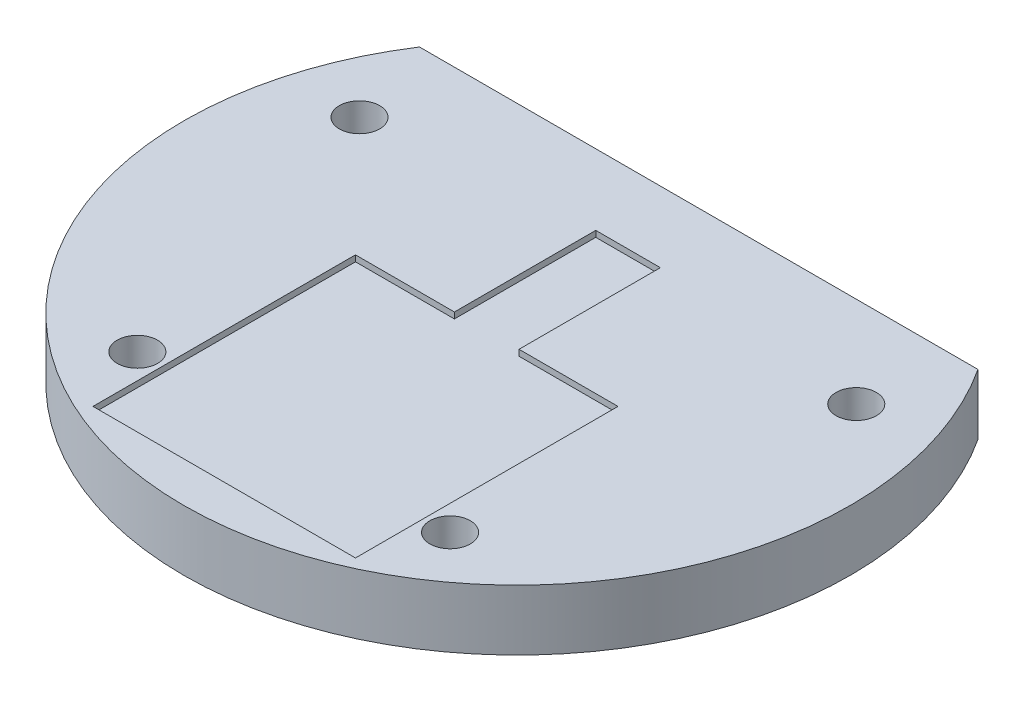
SolidWorks part; units mm, degrees
ref_plane "前视基准面" through (0, 0, 0) normal (0, 0, 1) x (1, 0, 0)
ref_plane "上视基准面" through (0, 0, 0) normal (0, 1, 0) x (1, 0, 0)
ref_plane "右视基准面" through (0, 0, 0) normal (1, 0, 0) x (0, 0, -1)
other "Configuration Table"
sketch "草图1" plane through (0, 0, 0) normal (0, 1, 0) x (1, 0, 0)
  circle A0 centre (0, 0) radius 16.5
  dimension "D1" = 33
extrude "凸台-拉伸1" add sketch "草图1" along normal blind 3
sketch "草图2" plane through (0, 3, 0) normal (0, 1, 0) x (1, 0, 0)
  line L1 (6.5, -14.5) -> (-6.5, -14.5)
  line L2 (6.5, -14.5) -> (6.5, -1.5)
  line L3 (6.5, -1.5) -> (-6.5, -1.5)
  line L4 (-6.5, -14.5) -> (-6.5, -1.5)
  line L5 (-6.5, -1.5) -> (6.5, -14.5) construction
  line L6 (0, -8) -> (0, 0)
  dimension "D1" = 13
  dimension "D2" = 8
extrude "切除-拉伸1" cut sketch "草图2" against normal blind 0.3 contours L3 L4 L1 L2
sketch "草图3" plane through (0, 3, 0) normal (0, 1, 0) x (1, 0, 0)
  line L0 (6.5, -1.5) -> (-6.5, -1.5) construction
  line L1 (1.6, -1.5) -> (-1.6, -1.5)
  line L2 (1.6, -1.5) -> (1.6, 5.5)
  line L3 (1.6, 5.5) -> (-1.6, 5.5)
  line L4 (-1.6, -1.5) -> (-1.6, 5.5)
  line L9 (0, 0) -> (0, 5.5) construction
  dimension "D1" = 3.2
  dimension "D2" = 7
extrude "切除-拉伸2" cut sketch "草图3" against normal up to surface (0.3 mm away) up to face at (0, 2.7, 8)
sketch "草图4" plane through (0, 0, 0) normal (0, -1, 0) x (1, 0, 0)
  circle A0 centre (-7.7433, 11.0586) radius 1
  circle A1 centre (7.7433, 11.0586) radius 1
  circle A2 centre (7.7433, 11.0586) radius 2
  circle A3 centre (-7.7433, 11.0586) radius 2
  circle A4 centre (-12.3, -4.5) radius 2
  circle A5 centre (-12.3, -4.5) radius 1
  circle A6 centre (12.3, -4.5) radius 2
  circle A7 centre (12.3, -4.5) radius 1
  point P12 (6.5, 11.1302)
  point P13 (7.7433, 11.0586)
  point P14 (-7.7433, 11.0586)
  point P15 (6.5, 11.0586)
  point P16 (8.4853, -8.3372)
  point P17 (12.4591, -3.4902)
  point P18 (12.3, -4.5)
  point P19 (-13.5777, -3.2831)
  point P20 (-12.3, -4.5)
  dimension "D1" = 2
  dimension "D2" = 4
extrude "切除-拉伸3" cut sketch "草图4" against normal blind 1.5
extrude "切除-拉伸4" cut sketch "草图4<2>" against normal through all contours A1 | A0 | A5 | A7 region at (7.7433, 0, 11.0586)
sketch "草图4<2>" plane through (0, 0, 0) normal (0, -1, 0) x (1, 0, 0) same geometry as "草图4"
sketch "草图5" plane through (0, 3, 0) normal (0, 1, 0) x (1, 0, 0)
  line L1 (13.8293, 9) -> (-13.8293, 9)
  line L2 (13.8293, 9) -> (13.8293, 18.0518)
  line L3 (13.8293, 18.0518) -> (-13.8293, 18.0518)
  line L4 (-13.8293, 9) -> (-13.8293, 18.0518)
  circle A0 centre (0, 0) radius 16.5 construction
  point P6 (-11.884, 9.631)
  point P8 (0, 0)
  dimension "D1" = 9
extrude "切除-拉伸5" cut sketch "草图5" against normal through all
